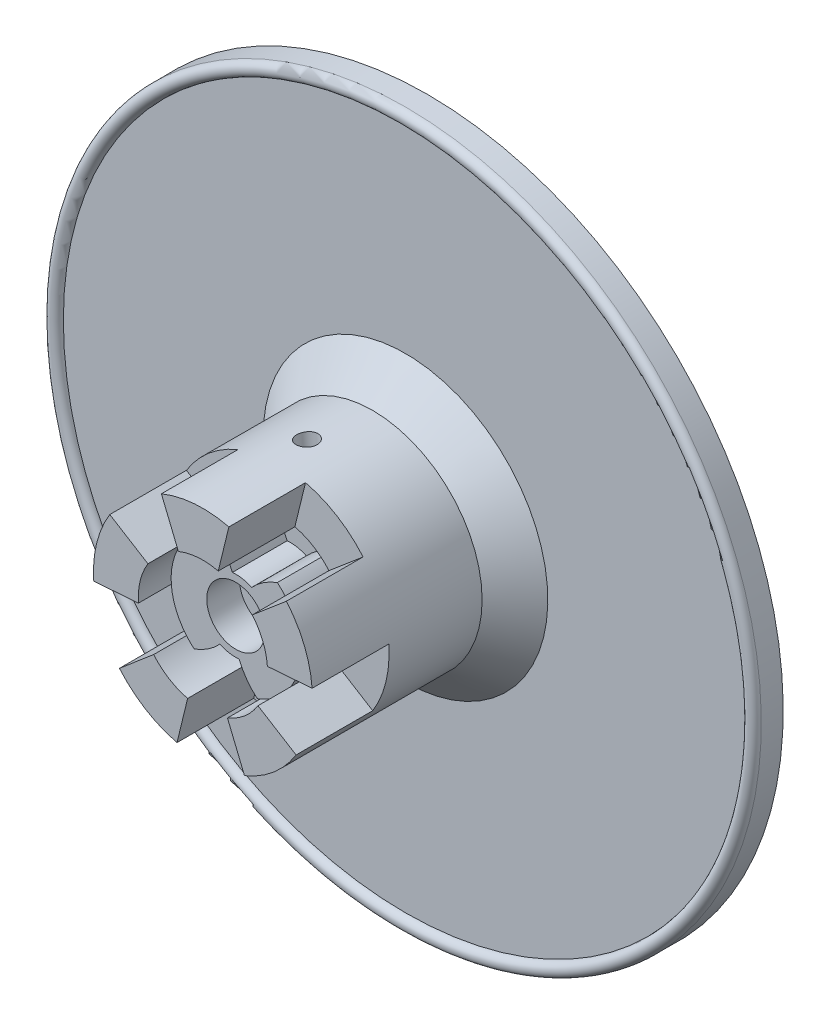
SolidWorks part; units mm, degrees
note: The reader was unsure of these and kept them because the rebuilt part matched: shared geometry of "Sketch11<5>", "Sketch11<6>".
ref_plane "Front Plane" through (0, 0, 0) normal (0, 0, 1) x (1, 0, 0)
ref_plane "Top Plane" through (0, 0, 0) normal (0, 1, 0) x (1, 0, 0)
ref_plane "Right Plane" through (0, 0, 0) normal (1, 0, 0) x (0, 0, -1)
sketch "Sketch2" plane through (0, 0, 0) normal (1, 0, 0) x (0, 0, -1)
  line L0 (-13.0175, 0) -> (-13.0175, 9.525)
  line L1 (-13.0175, -41.275) -> (13.0175, -41.275) construction
  line L2 (-13.0175, -41.275) -> (-13.0175, 9.525) construction
  line L3 (-9.8425, 41.275) -> (13.0175, 41.275) construction
  line L4 (13.0175, -41.275) -> (13.0175, 41.275) construction
  line L5 (-13.0175, -41.275) -> (13.0175, 41.275) construction
  line L6 (-13.0175, 41.275) -> (-9.8425, 31.2079) construction
  line L7 (-13.0175, 41.275) -> (-9.8425, 41.275) construction
  line L8 (-9.8425, 41.275) -> (-9.8425, 31.2079) construction
  line L9 (-9.8425, 12.7) -> (10.4775, 12.7)
  line L10 (10.4775, 12.7) -> (10.4775, 41.275)
  line L11 (10.4775, 41.275) -> (13.0175, 41.275)
  line L12 (13.0175, 41.275) -> (13.0175, 0)
  line L13 (13.0175, 0) -> (-13.0175, 0)
  line L14 (-13.0175, -41.275) -> (-13.0175, 0) construction
  line L15 (-9.8425, 12.7) -> (-13.0175, 12.7)
  line L16 (-9.8425, 31.2079) -> (-4.0054, 12.7) construction
  line L17 (-4.0054, 12.7) -> (13.0175, -41.275) construction
  line L18 (-9.8425, 31.2079) -> (-9.8425, 12.7) construction
  line L19 (-13.0175, 12.7) -> (-13.0175, 41.275) construction
  line L20 (-13.0175, 12.7) -> (-13.0175, 41.275) construction
  line L21 (-13.0175, 41.275) -> (-9.8425, 41.275) construction
  line L22 (-9.8425, 12.7) -> (-9.8425, 9.525) construction
  line L23 (-9.8425, 9.525) -> (-13.0175, 9.525) construction
  line L24 (-13.0175, 9.525) -> (-13.0175, 12.7)
  line L25 (-13.0175, 9.525) -> (-13.0175, 12.7) construction
  point P0 (0, 0)
  dimension "D1" = 82.55
  dimension "D2" = 26.035
  dimension "D3" = 3.175
  dimension "D4" = 12.7
  dimension "D5" = 2.54
  dimension "D6" = 9.525
revolve "Revolve1" add sketch "Sketch2" angle 360 about L13
sketch "Sketch11" plane through (0, 0, 13.0175) normal (0, 0, 1) x (1, 0, 0)
  circle A0 centre (0, 0) radius 3.3672 construction
  arc A1 (4.8195, 5.7465) -> (1.831, 3.7577) centre (7.3825, -1.3445) ccw construction
  arc A2 (1.831, 3.7577) -> (-0.3926, 4.1615) centre (0, 0) ccw construction
  arc A3 (0.3926, -4.1615) -> (2.4909, -7.0743) centre (7.3838, -1.3375) ccw construction
  arc A4 (-1.831, -3.7577) -> (0.3926, -4.1615) centre (0, 0) ccw construction
  arc A5 (-0.3926, 4.1615) -> (-2.4909, 7.0743) centre (-7.3838, 1.3375) ccw construction
  arc A6 (-4.8195, -5.7465) -> (-1.831, -3.7577) centre (-7.3825, 1.3445) ccw construction
  circle A7 centre (0, 0) radius 7.5 construction
  circle A8 centre (0, 0) radius 3.3672
  arc A9 (4.8195, 5.7465) -> (1.831, 3.7577) centre (7.3825, -1.3445) ccw
  arc A10 (1.831, 3.7577) -> (-0.3926, 4.1615) centre (0, 0) ccw
  arc A11 (0.3926, -4.1615) -> (2.4909, -7.0743) centre (7.3838, -1.3375) ccw
  arc A12 (-1.831, -3.7577) -> (0.3926, -4.1615) centre (0, 0) ccw
  arc A13 (-0.3926, 4.1615) -> (-2.4909, 7.0743) centre (-7.3838, 1.3375) ccw
  arc A14 (-4.8195, -5.7465) -> (-1.831, -3.7577) centre (-7.3825, 1.3445) ccw
  circle A15 centre (0, 0) radius 7.5
extrude "Cut-Extrude5" cut sketch "Sketch11" against normal blind 3.81 contours A14 A15 A11 A12 | A13 A15 A14 A12 A11 A9 A10 A8 | A8 | A9 A15 A13 A10
extrude "Cut-Extrude7" cut sketch "Sketch11<5>" against normal blind 7.62 contours A8
sketch "Sketch11<5>" plane through (0, 0, 13.0175) normal (0, 0, 1) x (1, 0, 0) same geometry as "Sketch11"
extrude "Cut-Extrude8" cut sketch "Sketch11<6>" against normal blind 10.16 contours A14 A15 A11 A12 | A9 A15 A13 A10
sketch "Sketch11<6>" plane through (0, 0, 13.0175) normal (0, 0, 1) x (1, 0, 0) same geometry as "Sketch11"
sketch "Sketch13" plane through (0, 0, -13.0175) normal (0, 0, -1) x (-1, 0, 0)
  circle A0 centre (0, 0) radius 6.35
extrude "Cut-Extrude10" cut sketch "Sketch13" against normal blind 12.192
chamfer "Chamfer1" distance 3.81 angle 45 1 edges at (-6.35, 0, -0.8255)
chamfer "Chamfer2" distance 3.81 angle 45 1 edges at (0, 12.7, -10.4775)
sketch "Sketch14" plane through (0, 0, 13.0175) normal (0, 0, 1) x (1, 0, 0)
  line L0 (9.6855, 8.2146) -> (5.7198, 4.8512) construction
  line L1 (12.6642, 0.9528) -> (7.4789, 0.5627) construction
  line L2 (-12.6642, -0.9528) -> (-7.4789, -0.5627)
  line L3 (-6.3813, 3.9408) -> (-10.8056, 6.673)
  line L4 (-12.6642, -0.9528) -> (-7.4789, -0.5627)
  line L5 (-6.3813, 3.9408) -> (-10.8056, 6.673)
  line L6 (-3.0073, -12.3388) -> (-1.776, -7.2867)
  line L7 (-5.7198, -4.8512) -> (-9.6855, -8.2146)
  line L8 (-3.0073, -12.3388) -> (-1.776, -7.2867)
  line L9 (-5.7198, -4.8512) -> (-9.6855, -8.2146)
  line L10 (2.8462, -6.939) -> (4.8196, -11.75)
  line L11 (10.8056, -6.673) -> (6.3813, -3.9408)
  line L12 (2.8462, -6.939) -> (4.8196, -11.75)
  line L13 (10.8056, -6.673) -> (6.3813, -3.9408)
  line L14 (1.776, 7.2867) -> (3.0073, 12.3388)
  line L15 (-4.8196, 11.75) -> (-2.8462, 6.939)
  line L16 (1.776, 7.2867) -> (3.0073, 12.3388)
  line L17 (-4.8196, 11.75) -> (-2.8462, 6.939)
  line L18 (9.6855, 8.2146) -> (5.7198, 4.8512)
  line L19 (12.6642, 0.9528) -> (7.4789, 0.5627)
  arc A0 (2.8462, -6.939) -> (6.3813, -3.9408) centre (0, 0) ccw construction
  circle A1 centre (0, 0) radius 7.5
  circle A2 centre (0, 0) radius 7.5
  arc A3 (12.6642, 0.9528) -> (9.6855, 8.2146) centre (0, 0) ccw construction
  arc A4 (-6.3813, 3.9408) -> (-7.4789, -0.5627) centre (0, 0) ccw
  arc A5 (-10.8056, 6.673) -> (-12.6642, -0.9528) centre (0, 0) ccw
  arc A6 (-6.3813, 3.9408) -> (-7.4789, -0.5627) centre (0, 0) ccw
  arc A7 (-10.8056, 6.673) -> (-12.6642, -0.9528) centre (0, 0) ccw
  arc A8 (-5.7198, -4.8512) -> (-1.776, -7.2867) centre (0, 0) ccw
  arc A9 (-9.6855, -8.2146) -> (-3.0073, -12.3388) centre (0, 0) ccw
  arc A10 (-5.7198, -4.8512) -> (-1.776, -7.2867) centre (0, 0) ccw
  arc A11 (-9.6855, -8.2146) -> (-3.0073, -12.3388) centre (0, 0) ccw
  arc A12 (2.8462, -6.939) -> (6.3813, -3.9408) centre (0, 0) ccw
  arc A13 (4.8196, -11.75) -> (10.8056, -6.673) centre (0, 0) ccw
  arc A14 (2.8462, -6.939) -> (6.3813, -3.9408) centre (0, 0) ccw
  arc A15 (4.8196, -11.75) -> (10.8056, -6.673) centre (0, 0) ccw
  arc A16 (1.776, 7.2867) -> (-2.8462, 6.939) centre (0, 0) ccw
  arc A17 (3.0073, 12.3388) -> (-4.8196, 11.75) centre (0, 0) ccw
  arc A18 (1.776, 7.2867) -> (-2.8462, 6.939) centre (0, 0) ccw
  arc A19 (3.0073, 12.3388) -> (-4.8196, 11.75) centre (0, 0) ccw
  arc A20 (-6.3813, 3.9408) -> (-7.4789, -0.5627) centre (0, 0) ccw construction
  arc A21 (-5.7198, -4.8512) -> (-1.776, -7.2867) centre (0, 0) ccw construction
  arc A22 (1.776, 7.2867) -> (-2.8462, 6.939) centre (0, 0) ccw construction
  arc A23 (2.8462, -6.939) -> (6.3813, -3.9408) centre (0, 0) ccw
  arc A24 (12.6642, 0.9528) -> (9.6855, 8.2146) centre (0, 0) ccw
  arc A25 (-6.3813, 3.9408) -> (-7.4789, -0.5627) centre (0, 0) ccw
  arc A26 (-5.7198, -4.8512) -> (-1.776, -7.2867) centre (0, 0) ccw
  arc A27 (1.776, 7.2867) -> (-2.8462, 6.939) centre (0, 0) ccw
  dimension "D1" = 0
  dimension "D2" = 0
  dimension "D3" = 0
  dimension "D4" = 0
  dimension "D5" = 0
extrude "Cut-Extrude11" cut sketch "Sketch14" against normal blind 8.89
ref_plane "Plane1" through (0.9061, -12.0444, 0) normal (0.075, -0.9972, 0) x (-0.9972, -0.075, 0)
ref_plane "Plane2" through (1.3825, -18.3765, 0) normal (0.075, -0.9972, 0) x (-0.9972, -0.075, 0)
hole_wizard "3/32 (0.09375) Diameter Hole1" positions "Sketch15" profile "Sketch16" hole size "3/32" standard "ANSI Inch" end condition through all
sketch "Sketch15" plane through (1.3825, -18.3765, 0) normal (0.075, -0.9972, 0) x (-0.9972, -0.075, 0)
  point P0 (0, 0)
sketch "Sketch16" plane through (1.3825, -18.3765, 0) normal (0, 0, 1) x (0.9972, 0.075, 0)
  line L0 (0, 0) -> (0, 62.6836)
  line L1 (0, 62.6836) -> (1.1906, 62.6836)
  line L2 (1.1906, 62.6836) -> (1.1906, 0)
  line L5 (1.1906, 0) -> (0, 0)
  line L11 (0, -6.35) -> (0, 107.95) construction
  dimension "Thru Hole Dia." = 2.3812
  dimension "Thru Hole Depth" = 62.6836
ref_axis "Axis1" through (0, 0, -15.0177) along (0, 0, 1)
sketch "Sketch17" plane through (0, 0, 0) normal (0, 1, 0) x (1, 0, 0)
  line L0 (-41.275, 10.4775) -> (41.275, 10.4775) construction
  line L1 (-41.275, 10.4775) -> (-39.6875, 10.4775)
  arc A0 (-41.275, 10.4775) -> (-39.6875, 10.4775) centre (-40.4812, 10.4775) ccw
  dimension "D1" = 1.5875
revolve "Revolve2" add sketch "Sketch17" angle 360 about axis through (0, 0, -15.0177) along (0, 0, 1)
